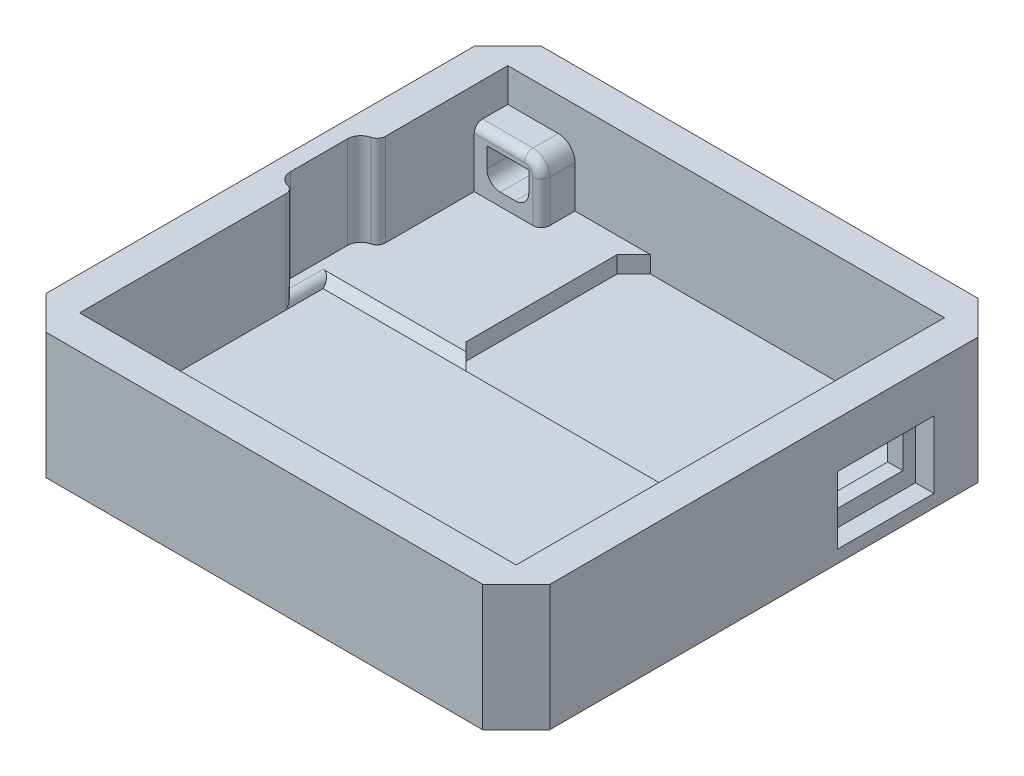
SolidWorks part; units mm, degrees
ref_plane "Front Plane" through (0, 0, 0) normal (0, 0, 1) x (1, 0, 0)
ref_plane "Top Plane" through (0, 0, 0) normal (0, 1, 0) x (1, 0, 0)
ref_plane "Right Plane" through (0, 0, 0) normal (1, 0, 0) x (0, 0, -1)
sketch "Sketch1" plane through (0, 0, 0) normal (0, 1, 0) x (1, 0, 0)
  line L1 (30, -29.5) -> (-30, -29.5)
  line L2 (30, -29.5) -> (30, 29.5)
  line L3 (30, 29.5) -> (-30, 29.5)
  line L4 (-30, -29.5) -> (-30, 29.5)
  line L5 (30, -29.5) -> (-30, 29.5) construction
  line L6 (30, 29.5) -> (-30, -29.5) construction
  point P0 (0, 0)
  dimension "D1" = 59
  dimension "D2" = 60
extrude "Boss-Extrude1" add sketch "Sketch1" along normal blind 4
sketch "Sketch2" plane through (0, 4, 0) normal (0, 1, 0) x (1, 0, 0)
  line L4 (-30, 29.5) -> (-30, -29.5)
  line L5 (-30, -29.5) -> (30, -29.5)
  line L6 (30, -29.5) -> (30, 29.5)
  line L7 (30, 29.5) -> (-30, 29.5)
  line L8 (-30, 29.5) -> (-30, -29.5)
  line L9 (-30, -29.5) -> (30, -29.5)
  line L10 (30, -29.5) -> (30, 29.5)
  line L11 (30, 29.5) -> (-30, 29.5)
  line L16 (-26, 25.5) -> (-26, -25.5)
  line L17 (-26, -25.5) -> (26, -25.5)
  line L18 (26, -25.5) -> (26, 25.5)
  line L19 (26, 25.5) -> (-26, 25.5)
  line L20 (-26, 25.5) -> (-26, -25.5)
  line L21 (-26, -25.5) -> (26, -25.5)
  line L22 (26, -25.5) -> (26, 25.5)
  line L23 (26, 25.5) -> (-26, 25.5)
  dimension "D1" = 0
  dimension "D2" = 4
extrude "Boss-Extrude2" add sketch "Sketch2" along normal blind 11 contours L22 L23 L20 L21
sketch "Sketch3" plane through (0, 4, 0) normal (0, 1, 0) x (1, 0, 0)
  line L0 (-9, 3.5) -> (-11, 5.5)
  line L1 (26, 25.5) -> (-9, 25.5)
  line L2 (26, 25.5) -> (26, 3.5)
  line L3 (26, 3.5) -> (-9, 3.5)
  line L4 (-11, 23.5) -> (-11, 5.5)
  line L5 (-9, 25.5) -> (-11, 23.5)
  point P1 (-11, 3.5)
  point P3 (-11, 25.5)
  dimension "D1" = 22
  dimension "D2" = 37
extrude "Cut-Extrude1" cut sketch "Sketch3" against normal blind 2
chamfer "Chamfer1" distance 4 angle 45 4 edges at (-30, 7.5, -29.5) (-30, 7.5, 29.5) (30, 7.5, 29.5) (30, 7.5, -29.5)
sketch "Sketch4" plane through (0, 4, 0) normal (0, 1, 0) x (1, 0, 0)
  line L1 (-26, 25.5) -> (-18, 25.5)
  line L2 (-26, 25.5) -> (-26, 21.5)
  line L3 (-26, 21.5) -> (-18, 21.5)
  line L4 (-18, 25.5) -> (-18, 21.5)
  dimension "D1" = 8
  dimension "D2" = 4
extrude "Boss-Extrude3" add sketch "Sketch4" along normal blind 7
sketch "Sketch5" plane through (0, 0, -21.5) normal (0, 0, 1) x (1, 0, 0)
  line L0 (-22, 11) -> (-22, 4) construction
  line L1 (-26, 11) -> (-18, 11) construction
  line L2 (-26, 4) -> (-18, 4) construction
  line L3 (-26, 7.5) -> (-18, 7.5) construction
  line L4 (-26, 11) -> (-26, 4) construction
  line L5 (-18, 11) -> (-18, 4) construction
  line L7 (-22.9, 5.5) -> (-21.1, 5.5)
  line L8 (-24.5, 7.1) -> (-24.5, 9.5)
  line L9 (-24.5, 9.5) -> (-19.5, 9.5)
  line L10 (-19.5, 7.1) -> (-19.5, 9.5)
  line L11 (-24.5, 5.5) -> (-19.5, 9.5) construction
  line L12 (-24.5, 9.5) -> (-19.5, 5.5) construction
  arc A0 (-19.5, 7.1) -> (-21.1, 5.5) centre (-21.1, 7.1) cw
  arc A1 (-24.5, 7.1) -> (-22.9, 5.5) centre (-22.9, 7.1) ccw
  point P12 (-22, 7.5)
  dimension "D3" = 1.6
  dimension "D4" = 1.6
  dimension "D1" = 5
  dimension "D2" = 4
extrude "Cut-Extrude2" cut sketch "Sketch5" against normal blind 6
sketch "Sketch6" plane through (0, 0, -27.5) normal (0, 0, 1) x (1, 0, 0)
  line L0 (-19.5, 9.5) -> (-24.5, 9.5) construction
  line L1 (-22.5, 9.5) -> (-21.5, 9.5)
  line L2 (-22.5, 9.5) -> (-22.5, 6.5)
  line L3 (-22.5, 6.5) -> (-21.5, 6.5)
  line L4 (-21.5, 9.5) -> (-21.5, 6.5)
  line L5 (-19.5, 7.1) -> (-19.5, 9.5) construction
  dimension "D1" = 3
  dimension "D2" = 1
  dimension "D3" = 2
extrude "Cut-Extrude3" cut sketch "Sketch6" against normal blind 6
fillet "Fillet1" radius 2 1 edges at (-18, 11, -23.5)
fillet "Fillet3" radius 1 3 edges at (-23, 11, -21.5) (-18.5858, 10.4142, -21.5) (-18, 6.5, -21.5)
sketch "Sketch7" plane through (0, 4, 0) normal (0, 1, 0) x (1, 0, 0)
  line L1 (26, 3.5) -> (-26, 3.5)
  line L2 (26, 3.5) -> (26, -25.5)
  line L3 (26, -25.5) -> (-26, -25.5)
  line L4 (-26, 3.5) -> (-26, -25.5)
extrude "Cut-Extrude4" cut sketch "Sketch7" against normal blind 1
chamfer "Chamfer2" distance 1 angle 45 1 edges at (-17.5, 4, -3.5)
sketch "Sketch8" plane through (0, 15, 0) normal (0, 1, 0) x (1, 0, 0)
  line L0 (-26, 25.5) -> (-26, -25.5) construction
  line L1 (-26, 0) -> (-26.4, 0)
  line L2 (-26, 0) -> (-26, 10)
  line L3 (-26, 10) -> (-26.4, 10)
  line L4 (-28, 1.6) -> (-28, 8.4)
  arc A0 (-28, 8.4) -> (-26.4, 10) centre (-26.4, 8.4) cw
  arc A1 (-28, 1.6) -> (-26.4, 0) centre (-26.4, 1.6) ccw
  point P8 (-28, 10)
  point P11 (-28, 0)
  dimension "D3" = 1.6
  dimension "D1" = 2
  dimension "D2" = 10
extrude "Cut-Extrude5" cut sketch "Sketch8" against normal blind 11
fillet "Fillet4" radius 1 1 edges at (-26, 4, -2.25)
fillet "Fillet5" radius 1 2 edges at (-26, 9.5, -10) (-26, 9, 0)
sketch "Sketch10" plane through (26, 0, 0) normal (-1, 0, 0) x (0, 0, 1)
  line L0 (-25.5, 15) -> (-25.5, 2) construction
  line L1 (-18.75, 3.5) -> (-10.25, 3.5)
  line L2 (-18.75, 3.5) -> (-18.75, 7.5)
  line L3 (-18.75, 7.5) -> (-10.25, 7.5)
  line L4 (-10.25, 3.5) -> (-10.25, 7.5)
  line L5 (-18.75, 3.5) -> (-10.25, 7.5) construction
  line L6 (-18.75, 7.5) -> (-10.25, 3.5) construction
  line L7 (-3.5, 2) -> (-25.5, 2) construction
  point P0 (-14.5, 5.5)
  dimension "D1" = 4
  dimension "D2" = 8.5
  dimension "D3" = 11
  dimension "D4" = 1.5
extrude "Cut-Extrude6" cut sketch "Sketch10" against normal blind 11
sketch "Sketch11" plane through (30, 0, 0) normal (1, 0, 0) x (0, 0, -1)
  line L1 (18.75, 7.5) -> (18.75, 3.5) construction
  line L2 (18.75, 5.5) -> (10.25, 5.5) construction
  line L3 (10.25, 3.5) -> (10.25, 7.5) construction
  line L4 (14.5, 3.5) -> (14.5, 7.5) construction
  line L5 (18.75, 3.5) -> (10.25, 3.5) construction
  line L6 (10.25, 7.5) -> (18.75, 7.5) construction
  line L8 (20.25, 9.5) -> (8.75, 9.5)
  line L9 (20.25, 9.5) -> (20.25, 1.5)
  line L10 (20.25, 1.5) -> (8.75, 1.5)
  line L11 (8.75, 9.5) -> (8.75, 1.5)
  line L12 (20.25, 9.5) -> (8.75, 1.5) construction
  line L13 (20.25, 1.5) -> (8.75, 9.5) construction
  point P12 (14.5, 5.5)
  dimension "D1" = 11.5
  dimension "D2" = 8
extrude "Cut-Extrude7" cut sketch "Sketch11" against normal blind 2.2
